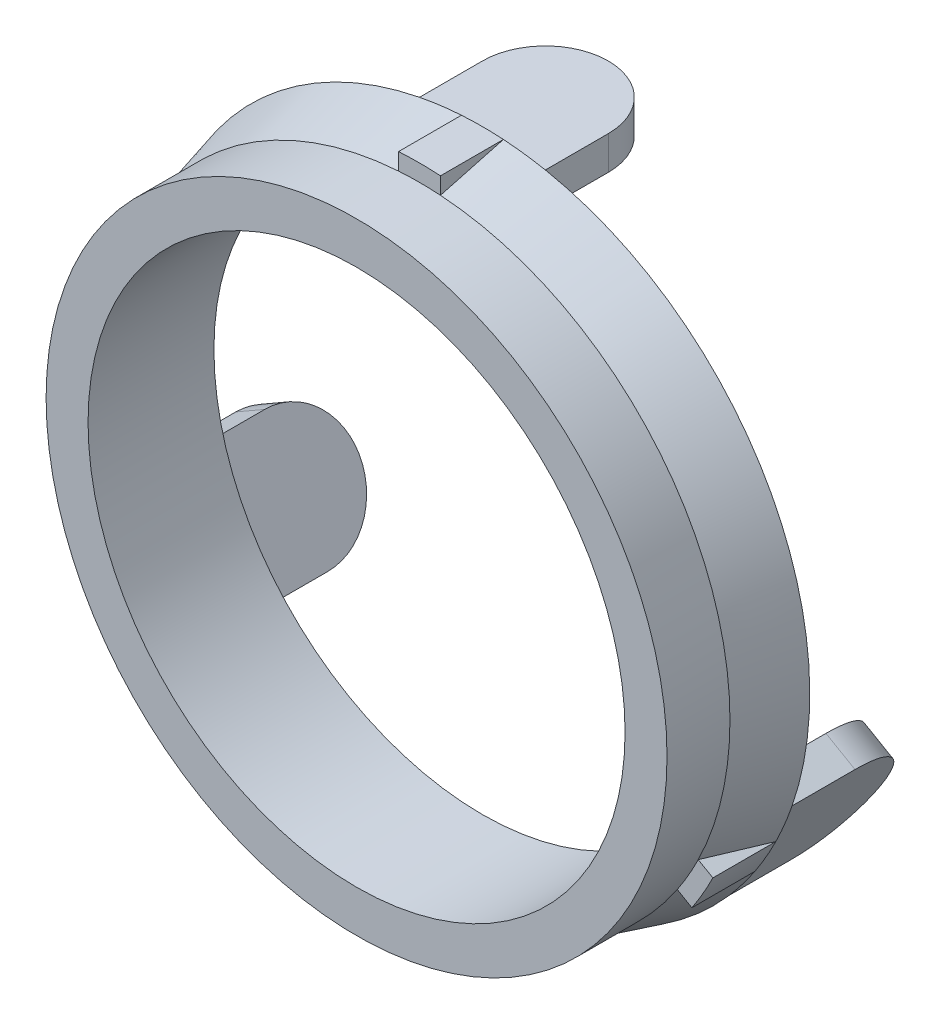
SolidWorks part; units mm, degrees
material "ABS"
ref_plane "Front Plane" through (0, 0, 0) normal (0, 0, 1) x (1, 0, 0)
ref_plane "Top Plane" through (0, 0, 0) normal (0, 1, 0) x (1, 0, 0)
ref_plane "Right Plane" through (0, 0, 0) normal (1, 0, 0) x (0, 0, -1)
sketch "Sketch2" plane through (0, 0, 0) normal (0, 1, 0) x (1, 0, 0)
  line L0 (0, -7.5) -> (0, 7.5) construction
  line L1 (37, 0) -> (37, -7.5)
  line L7 (37, 0) -> (39.0096, 7.5)
  line L12 (39.0096, 7.5) -> (32, 7.5)
  line L13 (32, 7.5) -> (32, -7.5)
  line L14 (32, -7.5) -> (37, -7.5)
  point P2 (0, 0)
  dimension "D1" = 15
  dimension "D2" = 37
  dimension "D3" = 5
  dimension "D4" = 15
  dimension "D5" = 7.5
revolve "Revolve1" add sketch "Sketch2" angle 360 about L0
sketch "Sketch3" plane through (0, 0, -7.5) normal (0, 0, -1) x (-1, 0, 0)
  line L0 (-2.5, 38.9294) -> (-2.5, 33.9294)
  line L1 (-2.5, 33.9294) -> (2.5, 33.9294)
  line L2 (2.5, 33.9294) -> (2.5, 38.9294)
  circle A0 centre (0, 0) radius 39.0096 construction
  arc A1 (-2.5, 38.9294) -> (2.5, 38.9294) centre (0, 0) cw
  point P7 (0, 33.9294)
  point P8 (0, 39.0096)
  dimension "D1" = 5
  dimension "D2" = 5
extrude "Boss-Extrude1" add sketch "Sketch3" along a picked direction on the side against the normal blind 7.5
sketch "Sketch6" plane through (0, 0, -7.5) normal (0, 0, -1) x (-1, 0, 0)
  line L1 (-7.5, 34.2819) -> (7.5, 34.2819)
  line L2 (-7.5, 34.2819) -> (-7.5, 38.2819)
  line L3 (-7.5, 38.2819) -> (7.5, 38.2819)
  line L4 (7.5, 34.2819) -> (7.5, 38.2819)
  arc A0 (-2.5, 38.9294) -> (2.5, 38.9294) centre (0, 0) ccw construction
  point P4 (0, 34.2819)
  point P8 (0, 0)
  point P10 (0, 0)
  dimension "D1" = 4
  dimension "D2" = 15
extrude "Boss-Extrude2" add sketch "Sketch6" along normal blind 15
fillet "Fillet1" radius 7.5 2 edges at (-7.5, 36.2819, -22.5) (7.5, 36.2819, -22.5)
pattern_circular "CirPattern1" count 3 over 360 about axis through (0, 0, 0) along (0, 0, 1) of "Boss-Extrude1", "Boss-Extrude2", "Fillet1"
